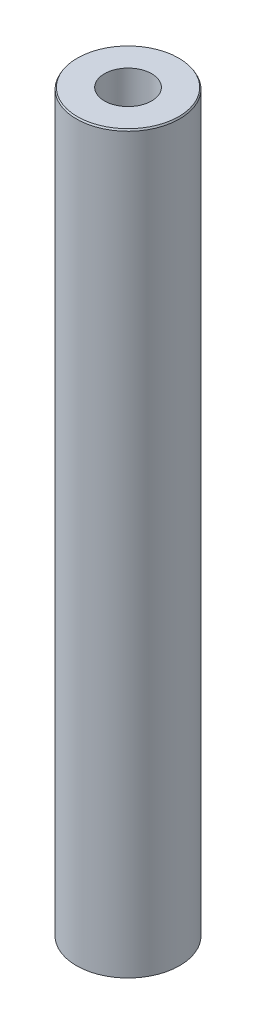
SolidWorks part; units mm, degrees
ref_plane "Front Plane" through (0, 0, 0) normal (0, 0, 1) x (1, 0, 0)
ref_plane "Top Plane" through (0, 0, 0) normal (0, 1, 0) x (1, 0, 0)
ref_plane "Right Plane" through (0, 0, 0) normal (1, 0, 0) x (0, 0, -1)
sketch "Sketch1" plane through (0, 0, 0) normal (0, 1, 0) x (1, 0, 0)
  circle A0 centre (0, 0) radius 27.5
  dimension "SHAFT_OD" = 55
extrude "Boss-Extrude1" add sketch "Sketch1" along normal blind 391.9977
sketch "Sketch2" plane through (0, 0, 0) normal (0, 1, 0) x (1, 0, 0)
  circle A0 centre (0, 0) radius 12.5858
  dimension "BORE_D" = 25.1716
extrude "Cut-Extrude1" cut sketch "Sketch2" along normal through all
chamfer "Chamfer1" distance 0.8407 angle 30 2 edges at (0, 391.9977, 27.5) (0, 0, 27.5) first distance on face at (0, 391.9977, 27.5) first distance on face at (0, 0, 12.5858)
